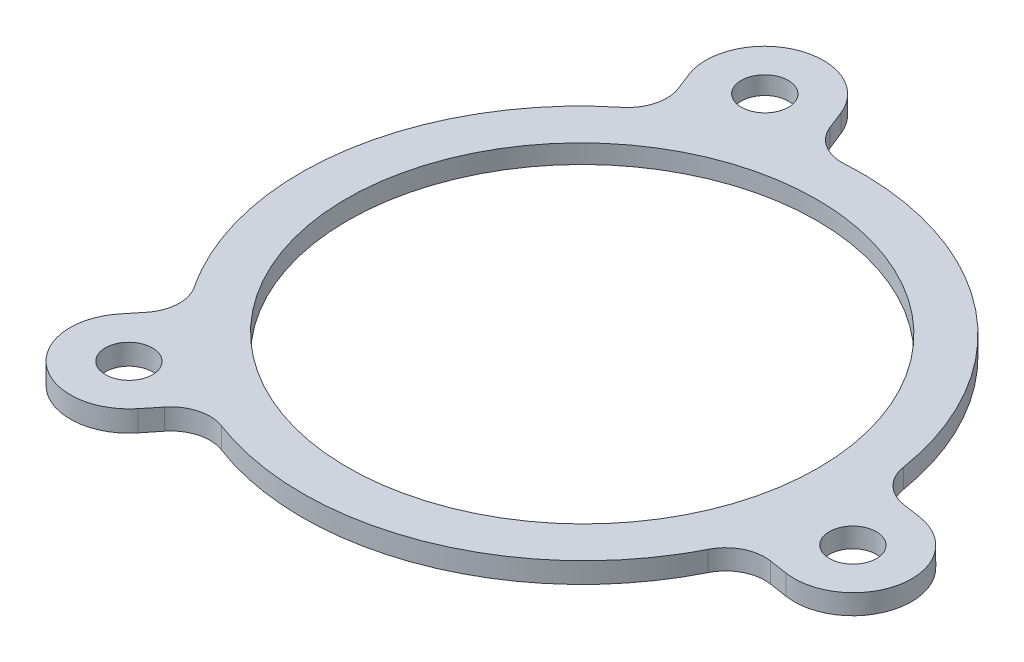
SolidWorks part; units mm, degrees
material "5454-O"
ref_plane "Front Plane" through (0, 0, 0) normal (0, 0, 1) x (1, 0, 0)
ref_plane "Top Plane" through (0, 0, 0) normal (0, 1, 0) x (1, 0, 0)
ref_plane "Right Plane" through (0, 0, 0) normal (1, 0, 0) x (0, 0, -1)
sketch "Sketch1" plane through (0, 0, 0) normal (0, 0, 1) x (1, 0, 0)
  line L0 (-3.7459, 1) -> (5.6477, 1) construction
  dimension "D1" = 1
ref_plane "Plane1" through (0, 1, -0.0051) normal (0, 1, -0.0051) x (1, 0, 0)
sketch "Sketch2" plane through (0, 0, 0) normal (0, 1, 0) x (1, 0, 0)
  line L0 (0, 0) -> (-6.0205, 15.3624) construction
  line L1 (0, 0) -> (-10.294, -12.8951) construction
  line L2 (0, 0) -> (16.3145, -2.4673) construction
  line L3 (-6.0205, 15.3624) -> (-3.2273, 16.4571) construction
  line L4 (-6.0205, 15.3624) -> (-8.8136, 14.2678) construction
  line L5 (-3.2273, 16.4571) -> (-2.3151, 14.1294) construction
  line L6 (-8.8136, 14.2678) -> (-7.9014, 11.9402) construction
  line L7 (16.3145, -2.4673) -> (16.7631, 0.4989) construction
  line L8 (16.3145, -2.4673) -> (15.8659, -5.4336) construction
  line L9 (16.7631, 0.4989) -> (14.2912, 0.8728) construction
  line L10 (15.8659, -5.4336) -> (13.394, -5.0598) construction
  line L11 (-10.294, -12.8951) -> (-7.9495, -14.7667) construction
  line L12 (-10.294, -12.8951) -> (-12.6386, -11.0234) construction
  line L13 (-12.6386, -11.0234) -> (-11.0789, -9.0696) construction
  line L14 (-7.9495, -14.7667) -> (-6.3898, -12.8129) construction
  line L15 (-8.8136, 14.2678) -> (-8.4608, 13.3674)
  line L16 (-3.2273, 16.4571) -> (-2.8744, 15.5566)
  line L17 (16.7631, 0.4989) -> (15.8069, 0.6436)
  line L18 (15.8659, -5.4336) -> (14.9097, -5.289)
  line L19 (-7.9495, -14.7667) -> (-7.3461, -14.0109)
  line L20 (-12.6386, -11.0234) -> (-12.0352, -10.2676)
  arc A0 (-8.8136, 14.2678) -> (-3.2273, 16.4571) centre (-6.0205, 15.3624) cw
  arc A1 (16.7631, 0.4989) -> (15.8659, -5.4336) centre (16.3145, -2.4673) cw
  arc A2 (-7.9495, -14.7667) -> (-12.6386, -11.0234) centre (-10.294, -12.8951) cw
  arc A3 (-0.8882, 14.2902) -> (14.1319, 2.2998) centre (0, 0) cw
  arc A4 (12.8198, -6.3759) -> (-5.0743, -13.3885) centre (0, 0) cw
  arc A5 (-11.9316, -7.9144) -> (-9.0576, 11.0887) centre (0, 0) cw
  arc A6 (-11.9316, -7.9144) -> (-12.0352, -10.2676) centre (-13.5983, -9.0199) cw
  arc A7 (12.8198, -6.3759) -> (14.9097, -5.289) centre (14.6106, -7.2665) cw
  arc A8 (-0.8882, 14.2902) -> (-2.8744, 15.5566) centre (-1.0123, 16.2864) cw
  arc A9 (-7.3461, -14.0109) -> (-5.0743, -13.3885) centre (-5.7831, -15.2587) cw
  arc A10 (15.8069, 0.6436) -> (14.1319, 2.2998) centre (16.1059, 2.6211) cw
  arc A11 (-9.0576, 11.0887) -> (-8.4608, 13.3674) centre (-10.3229, 12.6376) ccw
  circle A12 centre (0, 0) radius 12
  circle A13 centre (-6.0205, 15.3624) radius 1.2
  circle A14 centre (16.3145, -2.4673) radius 1.2
  circle A15 centre (-10.294, -12.8951) radius 1.2
  dimension "D1" = 2
  dimension "D2" = 2
extrude "Boss-Extrude1" add sketch "Sketch2" along normal up to surface (0.9278 mm away) up to plane "Plane1"
sketch3d "3DSketch2"
  point P0 (20.3145, 1.4781, 16.8951)
